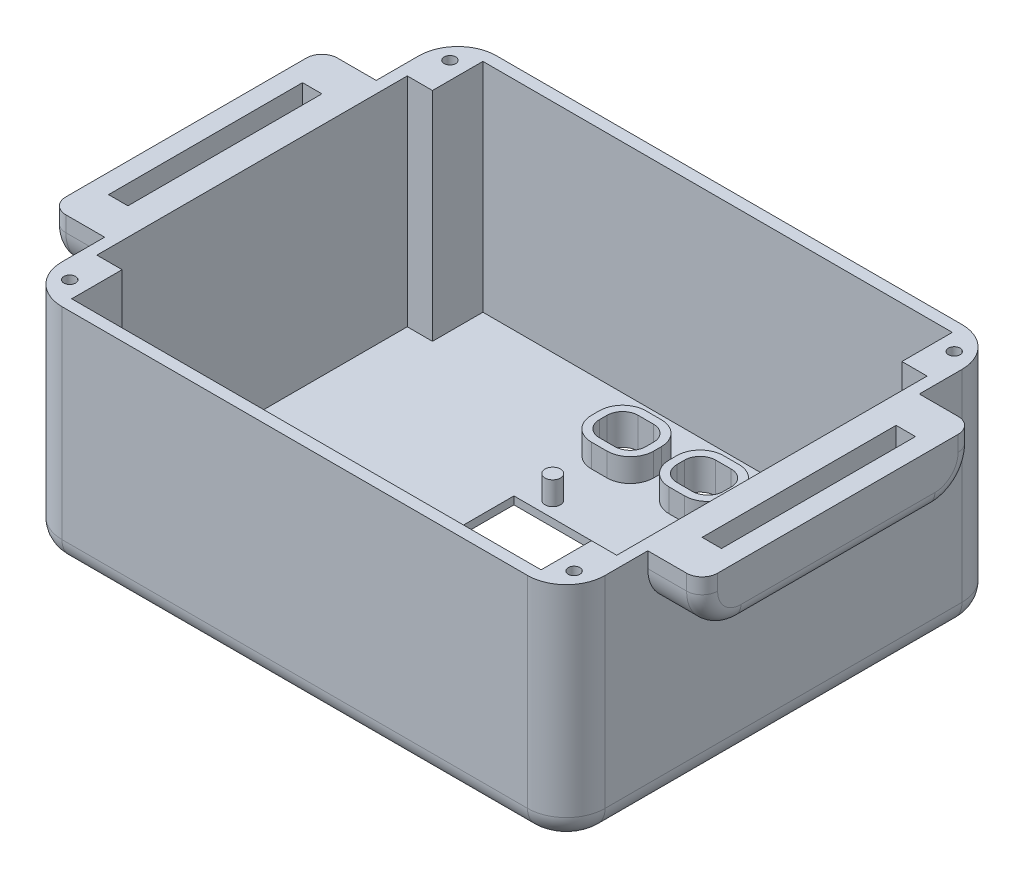
SolidWorks part; units mm, degrees
ref_plane "Front Plane" through (0, 0, 0) normal (0, 0, 1) x (1, 0, 0)
ref_plane "Top Plane" through (0, 0, 0) normal (0, 1, 0) x (1, 0, 0)
ref_plane "Right Plane" through (0, 0, 0) normal (1, 0, 0) x (0, 0, -1)
sketch "Sketch1" plane through (0, 0, 0) normal (0, 1, 0) x (1, 0, 0)
  line L0 (-29.25, 25) -> (29.25, 25) construction
  line L1 (-29.25, 25) -> (-29.25, 19) construction
  line L2 (-29.25, -25) -> (29.25, -25) construction
  line L3 (29.25, 25) -> (29.25, 19) construction
  line L4 (-7.75, 8) -> (18.25, 8) construction
  line L5 (-7.75, 8) -> (-7.75, -8) construction
  line L6 (-7.75, -8) -> (18.25, -8) construction
  line L7 (18.25, 8) -> (18.25, -8) construction
  line L9 (-35, 28) -> (35, 28)
  line L10 (-35, 28) -> (-35, -28)
  line L11 (-35, -28) -> (35, -28)
  line L12 (35, 28) -> (35, -28)
  line L16 (29.25, 19) -> (32.5, 19) construction
  line L17 (-32.5, 19) -> (-29.25, 19) construction
  line L18 (-32.5, 19) -> (-32.5, -19) construction
  line L19 (-32.5, -19) -> (-29.25, -19) construction
  line L20 (32.5, 19) -> (32.5, -19) construction
  line L21 (29.25, -19) -> (29.25, -25) construction
  line L22 (29.25, -19) -> (32.5, -19) construction
  line L23 (-29.25, -19) -> (-29.25, -25) construction
  line L24 (-33.5, 20) -> (-33.5, -20)
  line L25 (-30.25, -26.5) -> (30.25, -26.5)
  line L26 (33.5, 20) -> (33.5, -20)
  line L27 (-30.25, 26.5) -> (30.25, 26.5)
  line L28 (-30.25, 26.5) -> (-30.25, 20)
  line L29 (-30.25, 20) -> (-33.5, 20)
  line L30 (0, 0) -> (0, 38.588) construction
  line L31 (0, 0) -> (66.0787, 0) construction
  line L32 (30.25, 26.5) -> (30.25, 20)
  line L33 (30.25, 20) -> (33.5, 20)
  line L34 (30.25, -20) -> (33.5, -20)
  line L35 (30.25, -26.5) -> (30.25, -20)
  line L36 (-30.25, -20) -> (-33.5, -20)
  line L37 (-30.25, -26.5) -> (-30.25, -20)
  line L39 (-33.5, 26.5) -> (33.5, 26.5) construction
  line L40 (-33.5, 26.5) -> (-33.5, -26.5) construction
  line L41 (-33.5, -26.5) -> (33.5, -26.5) construction
  line L42 (33.5, 26.5) -> (33.5, -26.5) construction
  point P8 (0, 25)
  point P10 (-35, 0)
  point P11 (0, 28)
  point P17 (-32.5, 0)
  dimension "D1" = 50
  dimension "D2" = 58.5
  dimension "D3" = 26
  dimension "D4" = 16
  dimension "D5" = 17
  dimension "D6" = 11
  dimension "D7" = 70
  dimension "D8" = 56
  dimension "D10" = 65
  dimension "D9" = 3.25
  dimension "D11" = 38
  dimension "D12" = 25
  dimension "D13" = 32.5
  dimension "D15" = 1
  dimension "D16" = 1
  dimension "D14" = 1.5
extrude "Boss-Extrude3" add sketch "Sketch1" along normal blind 28
sketch "Sketch3" plane through (0, 0, 0) normal (0, -1, 0) x (1, 0, 0)
  line L0 (-35, -28) -> (-35, 28) construction
  line L1 (-35, 28) -> (35, 28)
  line L2 (-35, 28) -> (-35, -28)
  line L3 (-35, -28) -> (35, -28)
  line L4 (35, 28) -> (35, -28)
  line L5 (-35, 28) -> (35, 28) construction
  line L6 (35, 28) -> (35, -28) construction
  line L7 (35, -28) -> (-35, -28) construction
extrude "Boss-Extrude4" add sketch "Sketch3" along normal blind 1
sketch "Sketch4" plane through (0, -1, 0) normal (0, -1, 0) x (-1, 0, 0)
  line L0 (35, 28) -> (-35, 28) construction
  line L1 (7.75, -8) -> (-18.25, -8)
  line L2 (7.75, -8) -> (7.75, 8)
  line L3 (7.75, 8) -> (-18.25, 8)
  line L4 (-18.25, -8) -> (-18.25, 8)
  line L5 (35, -28) -> (35, 28) construction
  dimension "D1" = 20
  dimension "D2" = 27.25
  dimension "D3" = 16
  dimension "D4" = 26
extrude "Cut-Extrude1" cut sketch "Sketch4" against normal blind 1
sketch "Sketch5" plane through (0, -1, 0) normal (0, -1, 0) x (1, 0, 0)
  line L0 (-7.75, -8) -> (18.25, -8) construction
  line L1 (-5.75, -17) -> (-3.75, -17)
  line L2 (-7.75, -19) -> (-7.75, -20)
  line L3 (-5.75, -22) -> (-3.75, -22)
  line L4 (-1.75, -19) -> (-1.75, -20)
  line L13 (-7.75, 8) -> (-7.75, -8) construction
  line L15 (4.25, -17) -> (6.25, -17)
  line L16 (2.25, -19) -> (2.25, -20)
  line L17 (8.25, -19) -> (8.25, -20)
  line L18 (4.25, -22) -> (6.25, -22)
  line L19 (14.25, -17) -> (16.25, -17)
  line L20 (12.25, -19) -> (12.25, -20)
  line L21 (18.25, -19) -> (18.25, -20)
  line L22 (14.25, -22) -> (16.25, -22)
  line L23 (-7.75, -17) -> (2.25, -17) construction
  arc A0 (16.25, -17) -> (18.25, -19) centre (16.25, -19) cw
  arc A1 (18.25, -20) -> (16.25, -22) centre (16.25, -20) cw
  arc A2 (12.25, -20) -> (14.25, -22) centre (14.25, -20) ccw
  arc A3 (14.25, -17) -> (12.25, -19) centre (14.25, -19) ccw
  arc A4 (8.25, -20) -> (6.25, -22) centre (6.25, -20) cw
  arc A5 (2.25, -20) -> (4.25, -22) centre (4.25, -20) ccw
  arc A6 (6.25, -17) -> (8.25, -19) centre (6.25, -19) cw
  arc A7 (4.25, -17) -> (2.25, -19) centre (4.25, -19) ccw
  arc A8 (-3.75, -22) -> (-1.75, -20) centre (-3.75, -20) ccw
  arc A9 (-3.75, -17) -> (-1.75, -19) centre (-3.75, -19) cw
  arc A10 (-7.75, -20) -> (-5.75, -22) centre (-5.75, -20) ccw
  arc A11 (-5.75, -17) -> (-7.75, -19) centre (-5.75, -19) ccw
  point P34 (2.25, -17)
  point P39 (-1.75, -17)
  point P44 (-7.75, -17)
  dimension "D7" = 2
  dimension "D1" = 14
  dimension "D2" = 9
  dimension "D3" = 0
  dimension "D4" = 6
  dimension "D5" = 3
  dimension "D6" = 10
extrude "Cut-Extrude2" cut sketch "Sketch5" against normal blind 1
sketch "Sketch6" plane through (0, 28, 0) normal (0, 1, 0) x (1, 0, 0)
  line L1 (-35, 28) -> (-35, -28) construction
  line L3 (35, 28) -> (-35, 28) construction
  line L4 (0, 0) -> (0, 31.8703) construction
  line L5 (-51.24, 0) -> (49.0765, 0) construction
  circle A0 centre (-32.5, 24.5) radius 0.75
  circle A1 centre (32.5, 24.5) radius 0.75
  circle A2 centre (32.5, -24.5) radius 0.75
  circle A3 centre (-32.5, -24.5) radius 0.75
  dimension "D1" = 1.5
  dimension "D2" = 2.5
  dimension "D3" = 3.5
extrude "Cut-Extrude3" cut sketch "Sketch6" against normal blind 15
sketch "Sketch9" plane through (0, -1, 0) normal (0, -1, 0) x (1, 0, 0)
  line L1 (19.8499, 12.9704) -> (-32.6869, 12.9704)
sketch "Sketch8" plane through (0, -1, 0) normal (0, -1, 0) x (-1, 0, 0)
  text T0 "<b><i>Forza</i></b>" font "Garamond" height in points 36
extrude "Cut-Extrude4" cut sketch "Sketch8" against normal blind 0.25
fillet "Fillet2" radius 3 4 edges at (35, -1, 0) (0, -1, -28) (-35, -1, 0) (0, -1, 28)
fillet "Fillet3" radius 5 8 edges at (-34.1213, -0.1213, 27.1213) (34.1213, -0.1213, 27.1213) (-34.1213, -0.1213, -27.1213) (34.1213, -0.1213, -27.1213) (35, 15, -28) (-35, 15, -28) (35, 15, 28) (-35, 15, 28)
sketch "Sketch11" plane through (0, 0, 0) normal (0, 1, 0) x (1, 0, 0)
  line L0 (-5.75, 17) -> (-3.75, 17)
  line L1 (-1.75, 19) -> (-1.75, 20)
  line L2 (-3.75, 22) -> (-5.75, 22)
  line L3 (-7.75, 20) -> (-7.75, 19)
  line L4 (-5.75, 17) -> (-3.75, 17)
  line L5 (-1.75, 19) -> (-1.75, 20)
  line L6 (-3.75, 22) -> (-5.75, 22)
  line L7 (6.25, 23) -> (4.25, 23)
  line L8 (9.25, 19) -> (9.25, 20)
  line L9 (4.25, 16) -> (6.25, 16)
  line L10 (1.25, 20) -> (1.25, 19)
  line L11 (6.25, 22) -> (4.25, 22)
  line L12 (8.25, 19) -> (8.25, 20)
  line L13 (4.25, 17) -> (6.25, 17)
  line L14 (2.25, 20) -> (2.25, 19)
  line L15 (16.25, 23) -> (14.25, 23)
  line L16 (19.25, 19) -> (19.25, 20)
  line L17 (14.25, 16) -> (16.25, 16)
  line L18 (11.25, 20) -> (11.25, 19)
  line L19 (16.25, 22) -> (14.25, 22)
  line L20 (18.25, 19) -> (18.25, 20)
  line L21 (14.25, 17) -> (16.25, 17)
  line L22 (12.25, 20) -> (12.25, 19)
  line L44 (-8.75, 20) -> (-8.75, 19)
  line L45 (-0.75, 19) -> (-0.75, 20)
  line L46 (-5.75, 16) -> (-3.75, 16)
  line L47 (-3.75, 23) -> (-5.75, 23)
  line L48 (-8.75, 20) -> (-8.75, 19)
  line L49 (-0.75, 19) -> (-0.75, 20)
  line L50 (-5.75, 16) -> (-3.75, 16)
  line L51 (-3.75, 23) -> (-5.75, 23)
  arc A0 (-3.75, 17) -> (-1.75, 19) centre (-3.75, 19) ccw
  arc A1 (-1.75, 20) -> (-3.75, 22) centre (-3.75, 20) ccw
  arc A2 (-5.75, 22) -> (-7.75, 20) centre (-5.75, 20) ccw
  arc A3 (-7.75, 19) -> (-5.75, 17) centre (-5.75, 19) ccw
  arc A4 (-3.75, 17) -> (-1.75, 19) centre (-3.75, 19) ccw
  arc A5 (-1.75, 20) -> (-3.75, 22) centre (-3.75, 20) ccw
  arc A6 (-5.75, 22) -> (-7.75, 20) centre (-5.75, 20) ccw
  arc A7 (1.25, 19) -> (4.25, 16) centre (4.25, 19) ccw
  arc A8 (4.25, 23) -> (1.25, 20) centre (4.25, 20) ccw
  arc A9 (9.25, 20) -> (6.25, 23) centre (6.25, 20) ccw
  arc A10 (6.25, 16) -> (9.25, 19) centre (6.25, 19) ccw
  arc A11 (4.25, 22) -> (2.25, 20) centre (4.25, 20) ccw
  arc A12 (8.25, 20) -> (6.25, 22) centre (6.25, 20) ccw
  arc A13 (6.25, 17) -> (8.25, 19) centre (6.25, 19) ccw
  arc A14 (2.25, 19) -> (4.25, 17) centre (4.25, 19) ccw
  arc A15 (11.25, 19) -> (14.25, 16) centre (14.25, 19) ccw
  arc A16 (14.25, 23) -> (11.25, 20) centre (14.25, 20) ccw
  arc A17 (19.25, 20) -> (16.25, 23) centre (16.25, 20) ccw
  arc A18 (16.25, 16) -> (19.25, 19) centre (16.25, 19) ccw
  arc A19 (14.25, 22) -> (12.25, 20) centre (14.25, 20) ccw
  arc A20 (18.25, 20) -> (16.25, 22) centre (16.25, 20) ccw
  arc A21 (-5.75, 23) -> (-8.75, 20) centre (-5.75, 20) ccw
  arc A22 (-8.75, 19) -> (-5.75, 16) centre (-5.75, 19) ccw
  arc A23 (-3.75, 16) -> (-0.75, 19) centre (-3.75, 19) ccw
  arc A24 (-0.75, 20) -> (-3.75, 23) centre (-3.75, 20) ccw
  arc A25 (-5.75, 23) -> (-8.75, 20) centre (-5.75, 20) ccw
  arc A26 (-8.75, 19) -> (-5.75, 16) centre (-5.75, 19) ccw
  arc A27 (-3.75, 16) -> (-0.75, 19) centre (-3.75, 19) ccw
  arc A28 (-0.75, 20) -> (-3.75, 23) centre (-3.75, 20) ccw
  arc A29 (16.25, 17) -> (18.25, 19) centre (16.25, 19) ccw
  arc A30 (12.25, 19) -> (14.25, 17) centre (14.25, 19) ccw
  line M12 (18.25, 20) -> (18.25, 19)
  arc M13 (18.25, 19) -> (16.25, 17) centre (16.25, 19) cw
  line M14 (16.25, 17) -> (14.25, 17)
  arc M15 (14.25, 17) -> (12.25, 19) centre (14.25, 19) cw
  line M16 (12.25, 19) -> (12.25, 20)
  arc M17 (12.25, 20) -> (14.25, 22) centre (14.25, 20) cw
  line M18 (14.25, 22) -> (16.25, 22)
  arc M19 (16.25, 22) -> (18.25, 20) centre (16.25, 20) cw
  line M20 (4.25, 22) -> (6.25, 22)
  arc M21 (6.25, 22) -> (8.25, 20) centre (6.25, 20) cw
  line M22 (8.25, 20) -> (8.25, 19)
  arc M23 (8.25, 19) -> (6.25, 17) centre (6.25, 19) cw
  line M24 (6.25, 17) -> (4.25, 17)
  arc M25 (4.25, 17) -> (2.25, 19) centre (4.25, 19) cw
  line M26 (2.25, 19) -> (2.25, 20)
  arc M27 (2.25, 20) -> (4.25, 22) centre (4.25, 20) cw
  line M28 (-5.75, 22) -> (-3.75, 22)
  arc M29 (-3.75, 22) -> (-1.75, 20) centre (-3.75, 20) cw
  line M30 (-1.75, 20) -> (-1.75, 19)
  arc M31 (-1.75, 19) -> (-3.75, 17) centre (-3.75, 19) cw
  line M32 (-3.75, 17) -> (-5.75, 17)
  arc M33 (-5.75, 17) -> (-7.75, 19) centre (-5.75, 19) cw
  line M34 (-7.75, 19) -> (-7.75, 20)
  arc M35 (-7.75, 20) -> (-5.75, 22) centre (-5.75, 20) cw
  dimension "D1" = 1
  dimension "D2" = 1
  dimension "D3" = 1
  dimension "D4" = 3
extrude "Boss-Extrude5" add sketch "Sketch11" along normal blind 3 contours L49 A28 L51 A25 L48 A26 L50 A27 M35 M28 M29 M30 M31 M32 M33 M34 | L9 A10 L8 A9 L7 A8 L10 A7 M27 M20 M21 M22 M23 M24 M25 M26 | L17 A18 L16 A17 L15 A16 L18 A15 M19 M12 M13 M14 M15 M16 M17 M18 region at (8.2962, 0, -22.0462) region at (18.2962, 0, -22.0462) region at (-7.7962, 0, -22.0462)
sketch "Sketch12" plane through (0, 0, 0) normal (0, 1, 0) x (1, 0, 0)
  line L0 (18.25, -8) -> (-7.75, -8) construction
  line L1 (-7.75, -8) -> (-7.75, 8) construction
  line L2 (18.25, 8) -> (18.25, -8) construction
  line L3 (-7.75, 8) -> (18.25, 8) construction
  circle A0 centre (-4.75, -13.5) radius 1
  circle A1 centre (15.25, -13.5) radius 1
  circle A2 centre (15.25, 10) radius 1
  circle A3 centre (-4.75, 10) radius 1
  circle A4 centre (-4.75, 10) radius 1.5
  circle A5 centre (15.25, 10) radius 1.5
  circle A6 centre (-4.75, -13.5) radius 1.5
  circle A7 centre (15.25, -13.5) radius 1.5
  dimension "D1" = 2
  dimension "D2" = 2
  dimension "D3" = 2
  dimension "D4" = 2
  dimension "D11" = 3
  dimension "D12" = 3
  dimension "D13" = 3
  dimension "D14" = 3
  dimension "D5" = 5.5
  dimension "D6" = 3
  dimension "D7" = 3
  dimension "D8" = 5.5
  dimension "D9" = 2
  dimension "D10" = 2
extrude "Boss-Extrude6" add sketch "Sketch12" along normal blind 3 contours A0 | A2 | A1 | A3 | A3 region at (-4.75, 0, 13.5) region at (15.25, 0, 13.5) region at (15.25, 0, -10) region at (-4.75, 0, -10)
sketch "Sketch13" plane through (0, -1, 0) normal (0, -1, 0) x (1, 0, 0)
  line L0 (-6.4821, -12) -> (-6.4821, -16)
  line L1 (-6.4821, -16) -> (-3.0179, -14)
  line L2 (-3.0179, -14) -> (-6.4821, -12)
  line L3 (3.75, -12) -> (3.75, -16)
  line L4 (3.75, -16) -> (4.75, -16)
  line L5 (4.75, -16) -> (4.75, -12)
  line L6 (4.75, -12) -> (3.75, -12)
  line L7 (5.75, -12) -> (5.75, -16)
  line L8 (5.75, -16) -> (6.75, -16)
  line L9 (6.75, -16) -> (6.75, -12)
  line L10 (6.75, -12) -> (5.75, -12)
  line L11 (-6.1818, -12) -> (3.6675, -12) construction
  line L12 (-3.75, -17) -> (-5.75, -17) construction
  line L13 (6.25, -17) -> (4.25, -17) construction
  line L14 (-30, -25) -> (30, -25) construction
  line L15 (-27.5, 0.5) -> (-25.5, 0.5) construction
  line L16 (-27.5, -6) -> (-27.5, -7.5) construction
  line L17 (-27.5, -7.5) -> (-25.5, -7.5) construction
  line L18 (-25.5, 0.5) -> (-25.5, -2.5) construction
  line L19 (-16, 0.5) -> (-14, 0.5) construction
  line L20 (-16, 0.5) -> (-16, -2.5) construction
  line L21 (-16, -7.5) -> (-14, -7.5) construction
  line L22 (-14, 0.5) -> (-14, -1) construction
  line L23 (-25.5, -2.5) -> (-16, -2.5) construction
  line L25 (-25.5, -4.5) -> (-16, -4.5) construction
  line L27 (-32, 23) -> (-32, -23) construction
  line L28 (-25.5, -4.5) -> (-25.5, -7.5) construction
  line L29 (-16, -4.5) -> (-16, -7.5) construction
  line L30 (-20.75, 0) -> (-20.75, 6.6796) construction
  line L31 (-27.5, -1) -> (-29.25, -1) construction
  line L33 (-27.5, -6) -> (-29.25, -6) construction
  line L34 (-29.25, -1) -> (-29.25, -2.25) construction
  line L35 (-29.25, -2.25) -> (-30.75, -2.25) construction
  line L37 (-29.25, -4.75) -> (-30.75, -4.75) construction
  line L38 (-30.75, -2.25) -> (-30.75, -4.75) construction
  line L39 (-12.25, -2.25) -> (-10.75, -2.25) construction
  line L40 (-10.75, -2.25) -> (-10.75, -4.75) construction
  line L41 (-12.25, -4.75) -> (-10.75, -4.75) construction
  line L42 (-12.25, -1) -> (-12.25, -2.25) construction
  line L43 (-14, -6) -> (-12.25, -6) construction
  line L44 (-14, -1) -> (-12.25, -1) construction
  line L45 (-29.25, -4.75) -> (-29.25, -6) construction
  line L46 (-14, -6) -> (-14, -7.5) construction
  line L47 (-12.25, -4.75) -> (-12.25, -6) construction
  line L48 (-27.5, -1) -> (-27.5, 0.5) construction
  text T0 "Stats" font "Century Gothic" height in points 12
  point P19 (5.25, -17)
  point P20 (4.25, -16)
  point P21 (-4.75, -15)
  point P22 (-4.75, -17)
  point P34 (-26.5, -7.5)
  point P48 (-20.75, -2.5)
  dimension "D1" = 60
  dimension "D2" = 300
  dimension "D3" = 4
  dimension "D4" = 1
  dimension "D5" = 1
  dimension "D6" = 4
  dimension "D7" = 4
  dimension "D8" = 1
  dimension "D9" = 5
  dimension "D10" = 1
  dimension "D11" = 16
  dimension "D12" = 3.5
  dimension "D13" = 2
  dimension "D14" = 2
  dimension "D15" = 8
  dimension "D16" = 8
  dimension "D17" = 9.5
  dimension "D18" = 3
  dimension "D19" = 3
  dimension "D20" = 17.5
  dimension "D21" = 4.5
  dimension "D22" = 1.75
  dimension "D23" = 1.5
  dimension "D24" = 5
  dimension "D25" = 2.5
  dimension "D26" = 1.5
  dimension "D27" = 1.25
extrude "Cut-Extrude5" cut sketch "Sketch13" against normal blind 0.5
sketch "Sketch14" plane through (-35, 0, 0) normal (-1, 0, 0) x (0, 0, 1)
  line L0 (-23, 28) -> (23, 28) construction
  line L1 (-17.5, 28) -> (17.5, 28)
  line L2 (-17.5, 28) -> (-17.5, 21)
  line L3 (-17.5, 21) -> (17.5, 21)
  line L4 (17.5, 28) -> (17.5, 21)
  point P6 (0, 28)
  point P8 (0, 0)
  dimension "D1" = 7
  dimension "D2" = 35
extrude "Boss-Extrude8" add sketch "Sketch14" along normal blind 7
sketch "Sketch15" plane through (0, 21, 0) normal (0, -1, 0) x (1, 0, 0)
  line L0 (-35, -17.5) -> (-35, 17.5) construction
  line L5 (-39.5, 12.5) -> (-37, 12.5)
  line L6 (-39.5, 12.5) -> (-39.5, -12.5)
  line L7 (-39.5, -12.5) -> (-37, -12.5)
  line L8 (-37, 12.5) -> (-37, -12.5)
  point P6 (-37, 0)
  dimension "D1" = 2.5
  dimension "D2" = 2
  dimension "D3" = 25
extrude "Cut-Extrude6" cut sketch "Sketch15" against normal blind 15
fillet "Fillet5" radius 5 2 edges at (-38.5, 21, -17.5) (-38.5, 21, 17.5)
fillet "Fillet6" radius 2 5 edges at (-42, 27, -17.5) (-42, 27, 17.5) (-42, 22.4645, 16.0355) (-42, 22.4645, -16.0355) (-42, 21, 0)
mirror "Mirror3" about plane through (0, 0, 0) normal (1, 0, 0) of "Boss-Extrude8", "Cut-Extrude6", "Fillet5", "Fillet6"
